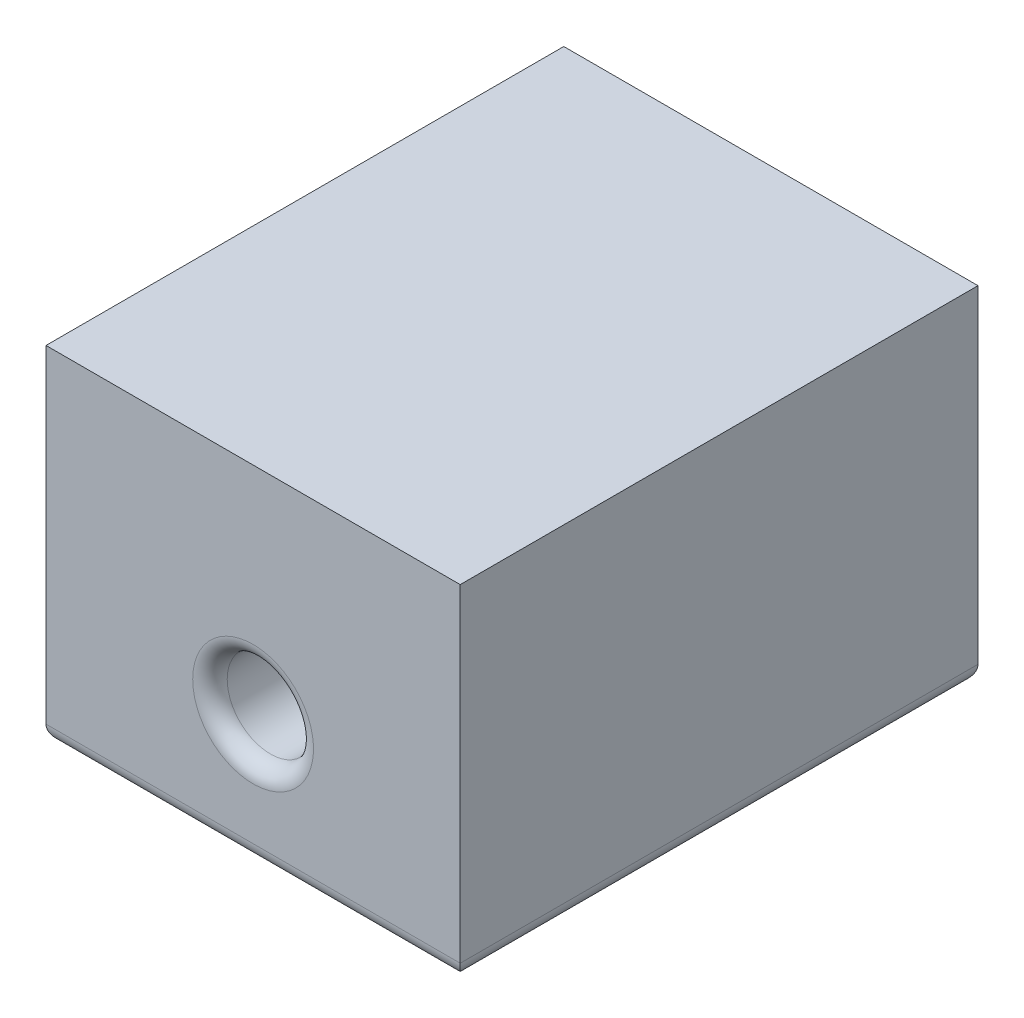
SolidWorks part; units mm, degrees
ref_plane "Front" through (0, 0, 0) normal (0, 0, 1) x (1, 0, 0)
ref_plane "Top" through (0, 0, 0) normal (0, 1, 0) x (1, 0, 0)
ref_plane "Right" through (0, 0, 0) normal (1, 0, 0) x (0, 0, -1)
sketch "Sketch1" plane through (0, 0, 0) normal (0, 1, 0) x (1, 0, 0)
  line L1 (0, 0) -> (24, 0)
  line L2 (0, 0) -> (0, 30)
  line L3 (0, 30) -> (24, 30)
  line L4 (24, 0) -> (24, 30)
  dimension "D1" = 24
  dimension "D2" = 30
extrude "Boss-Extrude1" add sketch "Sketch1" along normal blind 20
sketch "Sketch2" plane through (0, 0, -30) normal (0, 0, -1) x (-1, 0, 0)
  line L0 (-24, 0) -> (0, 0) construction
  circle A0 centre (-12, 7.5) radius 2.5
  point P5 (-12, 0)
  dimension "D1" = 5
  dimension "D2" = 7.5
extrude "Cut-Extrude1" cut sketch "Sketch2" against normal through all both and the other way through all
fillet "Fillet1" radius 1 6 edges at (14.5, 7.5, -30) (9.5, 7.5, 0) (12, 0, 0) (24, 0, -15) (12, 0, -30) (0, 0, -15)
ref_plane "Plane1" through (12, 0, 0) normal (-1, 0, 0) x (0, 0, 1)
sketch "Sketch3" plane through (12, 0, 0) normal (-1, 0, 0) x (0, 0, 1)
  spline S0 degree 3 poles (-63.2891, -8.1434) (-28.8406, 10.781) (-0.7696, 10.1937) (34.5814, -7.2489) (31.2266, -76.9312) (-54.9916, -73.6641) (-63.2891, -8.1434) (-28.8406, 10.781) (-0.7696, 10.1937) knots -0.566119 -0.306715 -0.103387 0 0.117759 0.222829 0.433881 0.693285 0.896613 1 1.117759 1.222829 1.433881 only from (-29.7703, 7.8984) to (-29.7703, 7.8984)
ref_plane "Plane2" through (0, 0, -15) normal (0, 0, -1) x (-1, 0, 0)
sketch "Sketch5" plane through (0, 0, -15) normal (0, 0, -1) x (-1, 0, 0)
  line L0 (-12, -71.039) -> (-12, 9.8285) construction
  circle A0 centre (-12, -71.039) radius 1
  dimension "D1" = 2
sweep "Sweep2" [suppressed] add path "Sketch3" circular profile diameter 2 parameters "D3"=2
